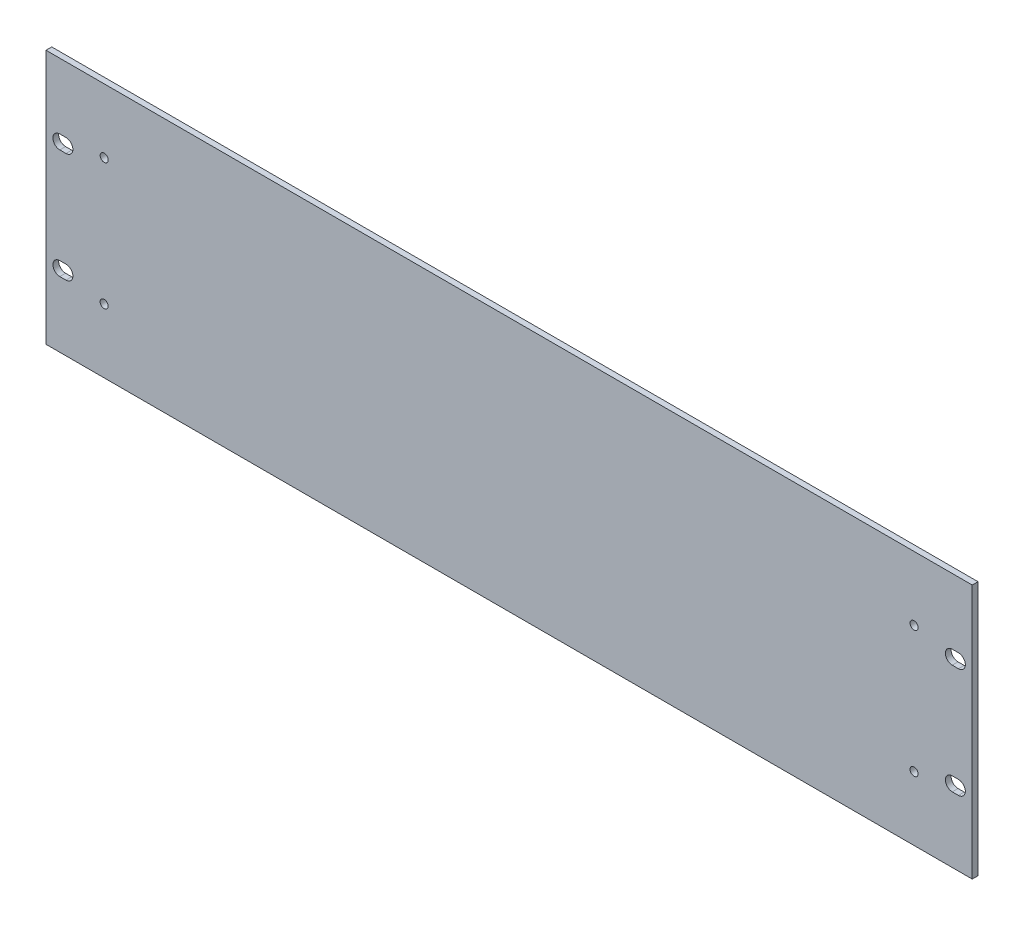
SolidWorks part; units mm, degrees
ref_plane "Front" through (0, 0, 0) normal (0, 0, 1) x (1, 0, 0)
ref_plane "Top" through (0, 0, 0) normal (0, 1, 0) x (1, 0, 0)
ref_plane "Right" through (0, 0, 0) normal (1, 0, 0) x (0, 0, -1)
sketch "Sketch1" plane through (0, 0, 0) normal (0, 0, 1) x (1, 0, 0)
  line L0 (0, 0) -> (-88.5937, 0) construction
  line L1 (0, 0) -> (241.3, 0)
  line L2 (0, 0) -> (0, 66.35)
  line L3 (0, 66.35) -> (241.3, 66.35)
  line L4 (241.3, 0) -> (241.3, 66.35)
  line L5 (0, 0) -> (0, -46.1923) construction
  line L6 (230.9, 32.175) -> (234.1, 32.175) construction
  line L7 (234.1, 24.975) -> (230.9, 24.975) construction
  line L8 (230.9, 28.575) -> (234.1, 28.575) construction
  line L9 (232.5, 28.575) -> (232.5, 0) construction
  line L10 (230.9, 28.575) -> (234.1, 28.575) construction
  line L11 (230.9, 32.175) -> (234.1, 32.175)
  line L12 (230.9, 24.975) -> (234.1, 24.975)
  arc A0 (234.1, 32.175) -> (234.1, 24.975) centre (234.1, 28.575) cw construction
  arc A1 (230.9, 24.975) -> (230.9, 32.175) centre (230.9, 28.575) cw construction
  circle A2 centre (211, 33) radius 2.1
  arc A3 (230.9, 32.175) -> (230.9, 24.975) centre (230.9, 28.575) ccw
  arc A4 (234.1, 24.975) -> (234.1, 32.175) centre (234.1, 28.575) ccw
  point P18 (232.5, 28.575)
  dimension "D5" = 10.4
  dimension "D6" = 422
  dimension "D7" = 4.2
  dimension "D1" = 482.6
  dimension "D2" = 465
  dimension "HEIGHT" = 132.7
  dimension "RackHole" = 57.15
  dimension "D4" = 7.2
  dimension "FixingHoles" = 66
sheet metal parameters "Sheet-Metal1" thickness 3 parameters "D1"=1.4
base flange "Base-Flange1" sketch "Sketch1" thickness 3 reverse thickness direction yes parameters "D1"=1.4
mirror "Mirror1" about plane through (0, 0, 3) normal (0, 1, 0) of bodies 101
mirror "Mirror2"
flat pattern "Flat-Pattern1" [suppressed]
sketch "Bend-Lines1" plane through (0, 0, 0) normal (0, 1, 0) x (-1, 0, 0)
sketch3d "Bounding-Box1" [suppressed]
  line L0 (-241.3, -177.1, 0) -> (241.3, -177.1, 0) construction
  line L1 (-241.3, 0, 0) -> (241.3, 0, 0) construction
  line L2 (-241.3, -177.1, 0) -> (-241.3, 0, 0) construction
  line L3 (241.3, -177.1, 0) -> (241.3, 0, 0) construction
